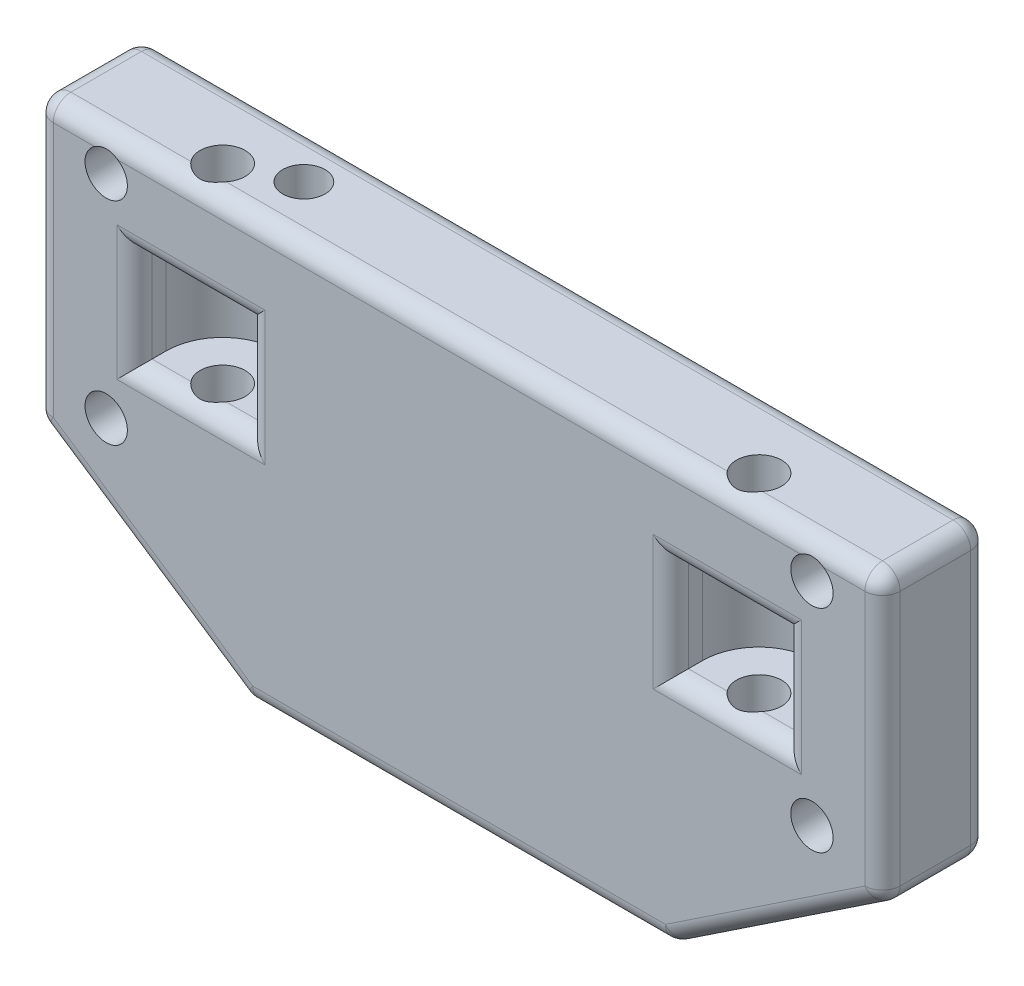
SolidWorks part; units mm, degrees
ref_plane "Front Plane" through (0, 0, 0) normal (0, 0, 1) x (1, 0, 0)
ref_plane "Top Plane" through (0, 0, 0) normal (0, 1, 0) x (1, 0, 0)
ref_plane "Right Plane" through (0, 0, 0) normal (1, 0, 0) x (0, 0, -1)
sketch "Sketch1" plane through (0, 0, 0) normal (0, 0, 1) x (1, 0, 0)
  line L0 (0, 0) -> (19.05, -12.7)
  line L2 (0, 0) -> (0, 25.4)
  line L3 (0, 25.4) -> (76.2, 25.4)
  line L4 (76.2, 0) -> (76.2, 25.4)
  line L5 (19.05, -12.7) -> (57.15, -12.7)
  line L6 (57.15, -12.7) -> (76.2, 0)
  dimension "D1" = 76.2
  dimension "D2" = 25.4
  dimension "D3" = 12.7
  dimension "D4" = 19.05
  dimension "D5" = 19.05
extrude "Boss-Extrude1" add sketch "Sketch1" along normal blind 9.525
ref_plane "Plane1" through (0, 12.7, 0) normal (0, 1, 0) x (1, 0, 0)
ref_plane "Plane2" through (38.1, 0, 0) normal (1, 0, 0) x (0, 0, -1)
sketch "Sketch2" plane through (0, 0, 9.525) normal (0, 0, 1) x (1, 0, 0)
  line L1 (0, 25.4) -> (0, 0) construction
  circle A0 centre (6.35, 22.225) radius 1.905
  dimension "D1" = 3.81
  dimension "D2" = 22.225
  dimension "D3" = 6.35
extrude "Cut-Extrude1" cut sketch "Sketch2" against normal through all
sketch "Sketch4" plane through (0, 12.7, 0) normal (0, 1, 0) x (1, 0, 0)
  line L7 (76.2, -9.525) -> (0, -9.525) construction
  line L8 (8.89, -6.6675) -> (8.89, -9.525)
  line L9 (19.05, -6.6675) -> (19.05, -9.525)
  line L10 (19.05, -9.525) -> (8.89, -9.525)
  line L11 (0, -9.525) -> (0, 0) construction
  arc A2 (19.05, -6.6675) -> (8.89, -6.6675) centre (13.97, -6.6675) ccw
  dimension "D1" = 10.16
  dimension "D2" = 2.8575
  dimension "D3" = 13.97
extrude "Cut-Extrude2" cut sketch "Sketch4" against normal mid plane 8.89
sketch "Sketch5" plane through (0, 25.4, 0) normal (0, 1, 0) x (1, 0, 0)
  line L0 (76.2, -9.525) -> (0, -9.525) construction
  line L1 (0, -9.525) -> (0, 0) construction
  circle A0 centre (13.97, -6.6675) radius 2.032
  dimension "D3" = 4.064
  dimension "D1" = 2.8575
  dimension "D2" = 13.97
extrude "Cut-Extrude3" cut sketch "Sketch5" against normal blind 28.575
sketch "Sketch13" plane through (0, 0, 0) normal (-1, 0, 0) x (0, 0, 1)
  line L0 (9.525, 25.4) -> (0, 25.4) construction
  line L1 (4.7625, 12.7) -> (0, 12.7) construction
  line L4 (4.7625, 12.7) -> (9.525, 12.7) construction
  circle A0 centre (4.7625, 12.7) radius 1.905
  dimension "D1" = 3.81
  dimension "D2" = 12.7
extrude "Cut-Extrude8" cut sketch "Sketch13" against normal blind 6.35
sketch "Sketch14" plane through (0, 0, 0) normal (0, 0, -1) x (-1, 0, 0)
  line L0 (-76.2, 25.4) -> (0, 25.4) construction
  line L1 (0, 25.4) -> (0, 0) construction
  circle A0 centre (-25.4, 22.225) radius 2.032
  dimension "D2" = 4.064
  dimension "D1" = 3.175
  dimension "D3" = 25.4
extrude "Cut-Extrude9" cut sketch "Sketch14" against normal blind 6.35
sketch "Sketch15" plane through (0, -12.7, 0) normal (0, -1, 0) x (1, 0, 0)
  line L0 (0, 9.525) -> (0, 0) construction
  line L1 (25.4, 0) -> (25.4, 4.7625) construction
  line L2 (19.05, 0) -> (57.15, 0) construction
  line L3 (25.4, 4.7625) -> (25.4, 9.525) construction
  line L4 (19.05, 9.525) -> (57.15, 9.525) construction
  circle A0 centre (25.4, 4.7625) radius 2.032
  point P5 (25.4, 9.525)
  dimension "D2" = 4.064
  dimension "D1" = 25.4
extrude "Cut-Extrude10" cut sketch "Sketch15" against normal blind 6.35
sketch "Sketch16" plane through (0, 25.4, 0) normal (0, 1, 0) x (1, 0, 0)
  line L0 (0, -9.525) -> (0, 0) construction
  line L1 (19.05, -4.4406) -> (19.05, 0.6437) construction
  line L2 (19.05, -4.4406) -> (19.05, -9.525) construction
  line L3 (76.2, 0) -> (0, 0) construction
  circle A0 centre (19.05, -4.4406) radius 1.905
  dimension "D2" = 3.81
  dimension "D1" = 19.05
extrude "Cut-Extrude11" cut sketch "Sketch16" against normal blind 6.35
mirror "Mirror1" about plane through (0, 12.7, 0) normal (0, 1, 0) of "Cut-Extrude1"
mirror "Mirror2" about plane through (38.1, 0, 0) normal (1, 0, 0) of "Cut-Extrude10", "Cut-Extrude9", "Cut-Extrude2", "Cut-Extrude1", "Mirror1", "Cut-Extrude3"
fillet "Fillet2" radius 1.5875 26 edges at (0, 0, 4.7625) (9.525, -6.35, 9.525) (19.05, -12.7, 4.7625) (9.525, -6.35, 0) (57.15, -12.7, 4.7625) (66.675, -6.35, 9.525) (66.675, -6.35, 0) (76.2, 0, 4.7625) (76.2, 12.7, 9.525) (76.2, 25.4, 4.7625) (76.2, 12.7, 0) (0, 25.4, 4.7625) (38.1, 25.4, 0) (0, 12.7, 0) (0, 12.7, 9.525) (38.1, -12.7, 9.525) (38.1, -12.7, 0) (62.23, 8.255, 9.525) (67.31, 12.7, 9.525) (62.23, 17.145, 9.525) (57.15, 12.7, 9.525) (19.05, 12.7, 9.525) (13.97, 17.145, 9.525) (8.89, 12.7, 9.525) (13.97, 8.255, 9.525) (38.1, 25.4, 9.525)
